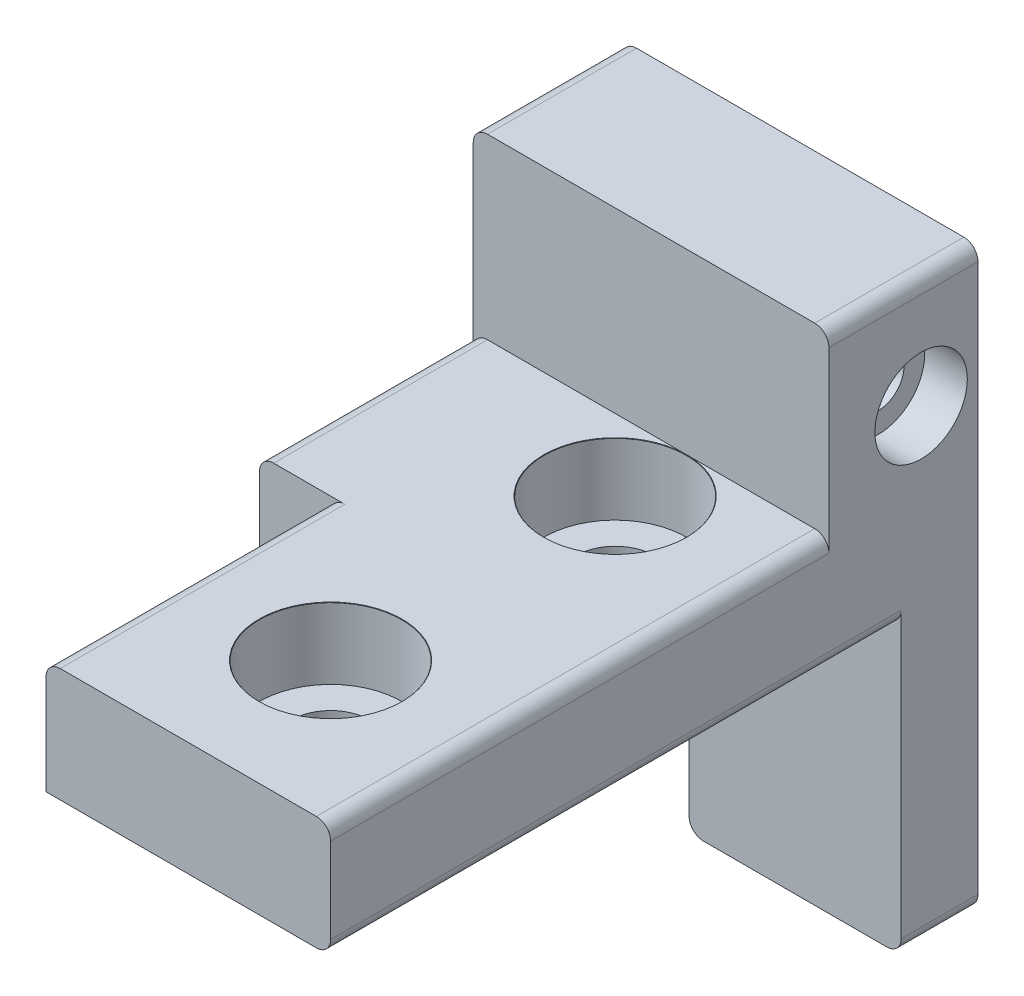
SolidWorks part; units mm, degrees
ref_plane "Front Plane" through (0, 0, 0) normal (0, 0, 1) x (1, 0, 0)
ref_plane "Top Plane" through (0, 0, 0) normal (0, 1, 0) x (1, 0, 0)
ref_plane "Right Plane" through (0, 0, 0) normal (1, 0, 0) x (0, 0, -1)
sketch "Sketch1" plane through (0, 0, 0) normal (0, 1, 0) x (1, 0, 0)
  line L0 (-10, 0) -> (-15, 0)
  line L1 (-10, -20) -> (10, -20)
  line L2 (-10, -20) -> (-10, 0)
  line L3 (-10, 20) -> (10, 20)
  line L4 (10, -20) -> (10, 20)
  line L5 (-10, -20) -> (10, 20) construction
  line L6 (-10, 20) -> (10, -20) construction
  line L7 (-15, 0) -> (-15, 20)
  line L8 (-15, 20) -> (-10, 20)
  point P0 (0, 0)
  dimension "D1" = 20
  dimension "D2" = 40
  dimension "D3" = 20
  dimension "D4" = 5
extrude "Boss-Extrude1" add sketch "Sketch1" along normal blind 8
sketch "Sketch2" plane through (0, 8, 0) normal (0, 1, 0) x (1, 0, 0)
  line L0 (0, -20) -> (0, 20) construction
  line L1 (-10, -20) -> (10, -20) construction
  line L2 (10, 20) -> (-15, 20) construction
  line L3 (-15, 10) -> (10, 10) construction
  line L4 (-15, 20) -> (-15, 0) construction
  line L5 (10, -20) -> (10, 20) construction
  point P14 (0, 10)
  point P15 (0, -10)
  dimension "D2" = 20
hole_wizard "CBORE for M5 SHCS1" positions "Sketch3" profile "Sketch4" counterbore size "M5" standard "ANSI Metric" end condition through all
sketch "Sketch3" plane through (0, 8, 0) normal (0, 1, 0) x (1, 0, 0)
  point P3 (0, 10)
  point P6 (0, -10)
sketch "Sketch4" plane through (0, 8, -10) normal (1, 0, 0) x (0, 0, 1)
  line L0 (0, 0) -> (0, 8)
  line L1 (0, 8) -> (2.75, 8)
  line L3 (2.75, 8) -> (2.75, 5)
  line L4 (5, 5) -> (2.75, 5)
  line L5 (5, 5) -> (5, 0.025)
  line L6 (5, 0.025) -> (5.025, 0)
  line L7 (5.025, 0) -> (0, 0)
  line L8 (-5, 0.025) -> (-5.025, 0) construction
  line L11 (0, -6.35) -> (0, 107.95) construction
  dimension "Thru Hole Dia." = 5.5
  dimension "Thru Hole Depth" = 8
  dimension "C'Bore Dia." = 10
  dimension "C'Bore Depth" = 5
  dimension "Near C'Sink Dia." = 10.05
  dimension "Near C'Sink Angle" = 90
sketch "Sketch5" plane through (0, 8, 0) normal (0, 1, 0) x (1, 0, 0)
  line L0 (10, -20) -> (10, 20) construction
  line L1 (-15, 18) -> (10, 18)
  line L2 (-15, 18) -> (-15, 15.025)
  line L3 (-15, 15.025) -> (10, 15.025)
  line L4 (10, 18) -> (10, 15.025)
  line L5 (10, 20) -> (-15, 20) construction
  line L6 (-15, 20) -> (-15, 0) construction
  circle A0 centre (0, 10) radius 5.025 construction
  dimension "D1" = 2
extrude "Boss-Extrude2" add sketch "Sketch5" along normal blind 12.51
sketch "Sketch6" plane through (0, 0, -18) normal (0, 0, -1) x (-1, 0, 0)
  line L0 (15, 20.51) -> (15, 8) construction
  line L1 (-10, 20.51) -> (15, 20.51)
  line L2 (-10, 20.51) -> (-10, 20)
  line L3 (-5, 17.51) -> (15, 17.51)
  line L4 (15, 20.51) -> (15, 17.51)
  line L5 (-5, 17.51) -> (-5, 8)
  line L6 (15, 8) -> (-10, 8) construction
  line L7 (-5, 8) -> (-10, 8)
  line L8 (-10, 8) -> (-10, 20)
  line L9 (15, 16.01) -> (12, 16.01)
  line L10 (12, 16.01) -> (12, 8)
  line L11 (-10, 8) -> (15, 8) construction
  line L12 (12, 8) -> (15, 8)
  line L13 (15, 8) -> (15, 16.01)
  dimension "D1" = 3
  dimension "D2" = 3
  dimension "D3" = 1.5
  dimension "D4" = 5
extrude "Boss-Extrude3" add sketch "Sketch6" along normal blind 7.5
sketch "Sketch7" plane through (0, 0, -20) normal (0, 0, -1) x (-1, 0, 0)
  line L6 (-10, 0) -> (15, 0)
  line L7 (15, 0) -> (15, 8)
  line L8 (15, 8) -> (12, 8)
  line L9 (12, 8) -> (-5, 8)
  line L10 (-5, 8) -> (-10, 8)
  line L11 (-10, 8) -> (-10, 0)
  line L12 (-10, 0) -> (15, 0)
  line L13 (15, 0) -> (15, 8)
  line L14 (15, 8) -> (12, 8)
  line L15 (12, 8) -> (-5, 8)
  line L16 (-5, 8) -> (-10, 8)
  line L17 (-10, 8) -> (-10, 0)
  dimension "D1" = 0
extrude "Boss-Extrude4" add sketch "Sketch7" along normal up to surface (5.5 mm away) up to face at (0, 15.34, -25.5)
sketch "Sketch8" plane through (0, 0, -18) normal (0, 0, -1) x (-1, 0, 0)
  line L0 (12, 16.01) -> (12, 8) construction
  line L1 (-5, 8) -> (12, 8)
  line L2 (-5, 8) -> (-5, 9.25)
  line L3 (-5, 9.25) -> (12, 9.25)
  line L4 (12, 8) -> (12, 9.25)
  dimension "D1" = 1.25
extrude "Boss-Extrude5" add sketch "Sketch8" along normal up to surface (7.5 mm away) up to face at (-5.4, 12.406, -25.5)
sketch "Sketch9" plane through (0, 0, -25.5) normal (0, 0, -1) x (-1, 0, 0)
  line L0 (-10, 0) -> (15, 0)
  line L1 (15, 0) -> (15, -5.4)
  line L2 (15, -5.4) -> (4.9, -5.4)
  line L3 (4.9, -5.4) -> (4.9, -20)
  line L4 (4.9, -20) -> (-10, -20)
  line L5 (-10, -20) -> (-10, 0)
  dimension "D1" = 5.4
  dimension "D2" = 10.1
  dimension "D3" = 20
extrude "Boss-Extrude6" add sketch "Sketch9" against normal blind 5.4
fillet "Fillet2" radius 1 10 edges at (-15, 0, -10.05) (10, 0, -0.05) (-10, 8, 10) (-15, 8, -7.5125) (10, 8, 2.4875) (-15, 20.51, -20.2625) (10, 20.51, -20.2625) (-15, -5.4, -22.8) (-4.9, -20, -22.8) (10, -20, -22.8)
sketch "Sketch10" plane through (10, 0, 0) normal (1, 0, 0) x (0, 0, -1)
  circle A0 centre (21.5, 12.75) radius 2.35 construction
  circle A1 centre (21.5, 12.75) radius 2.35
hole_wizard "CBORE for M3 SHCS1" positions "Sketch11" profile "Sketch12" counterbore size "M3" standard "ANSI Metric" end condition up to next
sketch "Sketch11" plane through (10, 0, 0) normal (1, 0, 0) x (0, 0, -1)
  point P0 (21.5, 12.75)
sketch "Sketch12" plane through (10, 12.75, -21.5) normal (0, 1, 0) x (0, 0, -1)
  line L0 (0, 0) -> (0, 5)
  line L1 (0, 5) -> (1.8, 5)
  line L3 (1.8, 5) -> (1.8, 3)
  line L4 (1.8, 3) -> (3.25, 3)
  line L5 (3.25, 3) -> (3.25, 0)
  line L7 (3.25, 0) -> (0, 0)
  line L11 (0, -6.35) -> (0, 107.95) construction
  dimension "Thru Hole Dia." = 3.6
  dimension "Thru Hole Depth" = 5
  dimension "C'Bore Dia." = 6.5
  dimension "C'Bore Depth" = 3
